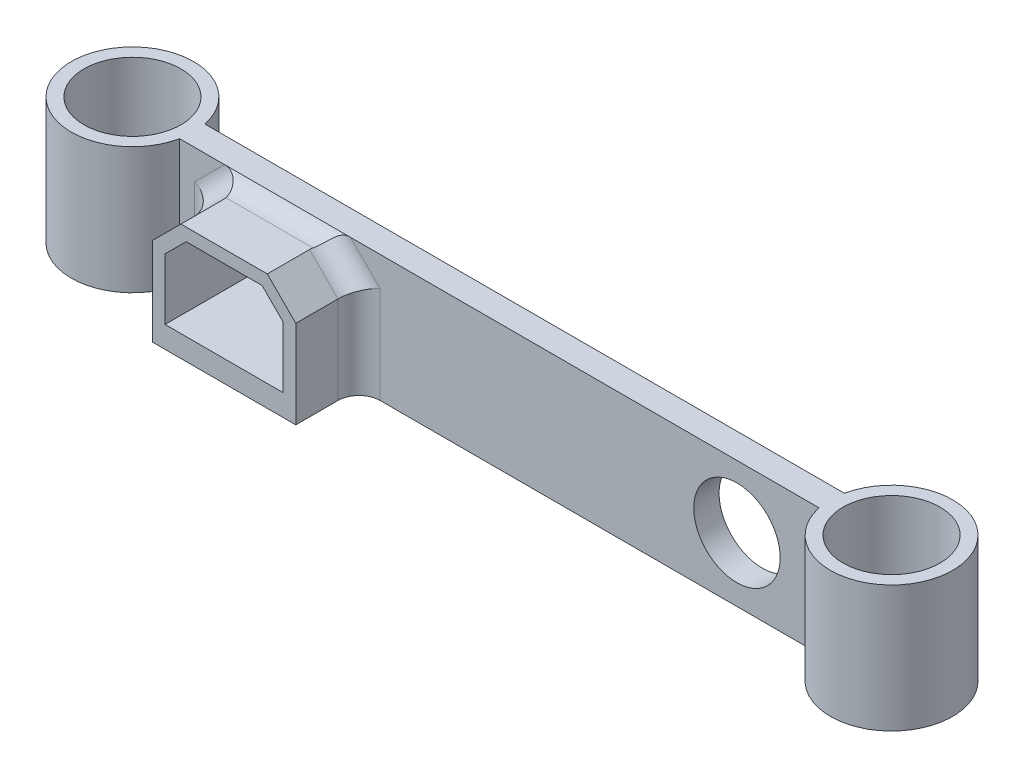
SolidWorks part; units mm, degrees
ref_plane "Front Plane" through (0, 0, 0) normal (0, 0, 1) x (1, 0, 0)
ref_plane "Top Plane" through (0, 0, 0) normal (0, 1, 0) x (1, 0, 0)
ref_plane "Right Plane" through (0, 0, 0) normal (1, 0, 0) x (0, 0, -1)
sketch "Sketch1" plane through (0, 0, 0) normal (0, 1, 0) x (1, 0, 0)
  line L0 (-28.3532, 3) -> (123.2743, 3)
  line L1 (-28.3532, -3) -> (123.2743, -3)
  line L2 (-31.0394, 0) -> (125.9606, 0) construction
  circle A0 centre (-42.5394, 0) radius 11.5
  circle A1 centre (137.4606, 0) radius 11.5
  arc A2 (-28.3532, -3) -> (-28.3532, 3) centre (-42.5394, 0) cw
  arc A3 (123.2743, 3) -> (123.2743, -3) centre (137.4606, 0) cw
  dimension "D3" = 23
  dimension "D4" = 23
  dimension "D5" = 180
  dimension "D6" = 3
  dimension "D7" = 3
  dimension "D1" = 6
  dimension "D2" = 3
extrude "Boss-Extrude1" add sketch "Sketch1" along normal blind 30
sketch "Sketch2" plane through (0, 0, 3) normal (0, 0, 1) x (1, 0, 0)
  line L0 (-11.8019, 24.6236) -> (6.1981, 24.6236)
  line L1 (11.1981, 24.6236) -> (11.1981, 5.1236)
  line L2 (11.1981, 5.1236) -> (-16.8019, 5.1236)
  line L3 (-16.8019, 5.1236) -> (-16.8019, 19.6236)
  line L4 (-16.8019, 19.6236) -> (-11.8019, 24.6236)
  line L5 (6.1981, 24.6236) -> (11.1981, 19.6236)
  dimension "D1" = 19.5
  dimension "D2" = 28
  dimension "D5" = 5
  dimension "D6" = 5
extrude "Cut-Extrude1" cut sketch "Sketch2" against normal blind 10 contours L5 L0 L4 L3 L2 L1
sketch "Sketch3" plane through (0, 0, 3) normal (0, 0, 1) x (1, 0, 0)
  line L0 (-11.8019, 24.6236) -> (-16.8019, 19.6236)
  line L1 (-16.8019, 19.6236) -> (-16.8019, 5.1236)
  line L2 (-16.8019, 5.1236) -> (11.1981, 5.1236)
  line L3 (11.1981, 5.1236) -> (11.1981, 19.6236)
  line L4 (11.1981, 19.6236) -> (6.1981, 24.6236)
  line L5 (6.1981, 24.6236) -> (-11.8019, 24.6236)
  line L6 (-13.0445, 27.6236) -> (7.4408, 27.6236)
  line L7 (7.4408, 27.6236) -> (14.1981, 20.8663)
  line L8 (14.1981, 20.8663) -> (14.1981, 2.1236)
  line L9 (14.1981, 2.1236) -> (-19.8019, 2.1236)
  line L10 (-19.8019, 2.1236) -> (-19.8019, 20.8663)
  line L11 (-19.8019, 20.8663) -> (-13.0445, 27.6236)
  point P14 (8.6981, 22.1236)
  point P19 (10.8195, 24.2449)
  dimension "D1" = 3
  dimension "D2" = 3
  dimension "D3" = 3
  dimension "D4" = 3
  dimension "D5" = 3
  dimension "D6" = 3
extrude "Boss-Extrude2" add sketch "Sketch3" along normal blind 15
sketch "Sketch4" plane through (0, 0, 3) normal (0, 0, 1) x (1, 0, 0)
  line L0 (-28.3532, 0) -> (123.2743, 0) construction
  line L1 (-19.8019, 2.1236) -> (14.1981, 2.1236)
  line L2 (-19.8019, 2.1236) -> (-19.8019, 0)
  line L3 (-19.8019, 0) -> (14.1981, 0)
  line L4 (14.1981, 2.1236) -> (14.1981, 0)
extrude "Boss-Extrude3" add sketch "Sketch4" along normal blind 15
fillet "Fillet1" radius 5 5 edges at (-19.8019, 10.4331, 3) (-16.4232, 24.2449, 3) (-2.8019, 27.6236, 3) (10.8195, 24.2449, 3) (14.1981, 10.4331, 3)
sketch "Sketch5" plane through (0, 0, -3) normal (0, 0, -1) x (-1, 0, 0)
  circle A0 centre (-103.8058, 15.14) radius 10.25
  point P2 (-103.8058, 15.14)
  dimension "D1" = 20.5
extrude "Cut-Extrude2" cut sketch "Sketch5" against normal blind 15
